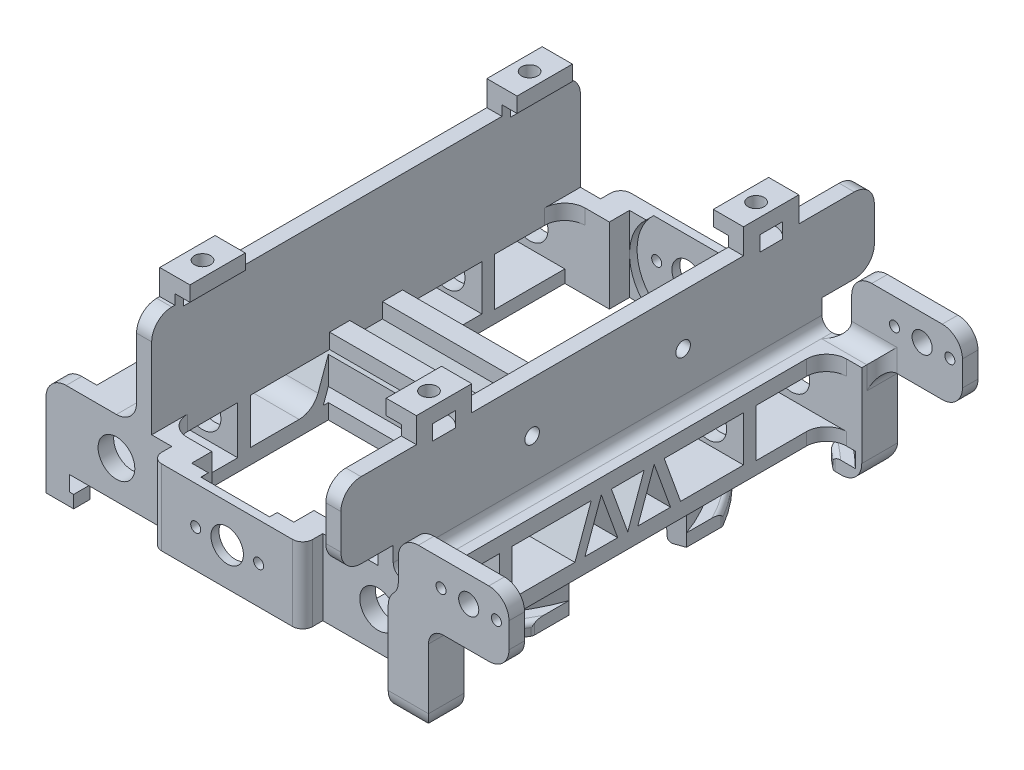
SolidWorks part; units mm, degrees
note: The reader was unsure of these and kept them because the rebuilt part matched: shared geometry of "草图50<4>".
ref_plane "前视基准面" through (0, 0, 0) normal (0, 0, 1) x (1, 0, 0)
ref_plane "上视基准面" through (0, 0, 0) normal (0, 1, 0) x (1, 0, 0)
ref_plane "右视基准面" through (0, 0, 0) normal (1, 0, 0) x (0, 0, -1)
sketch "草图1" plane through (0, 0, 0) normal (0, 0, 1) x (1, 0, 0)
  line L0 (-40, 0) -> (40, 0) construction
  line L1 (-40, 7.5) -> (40, 7.5)
  line L2 (-40, 7.5) -> (-40, -7.5)
  line L3 (-40, -7.5) -> (40, -7.5)
  line L4 (40, 7.5) -> (40, -7.5)
  line L5 (-40, 7.5) -> (40, -7.5) construction
  line L6 (-40, -7.5) -> (40, 7.5) construction
  line L7 (34, 6) -> (56, 6)
  line L8 (34, 6) -> (34, 19)
  line L9 (34, 19) -> (56, 19)
  line L10 (56, 6) -> (56, 19)
  point P0 (0, 0)
  dimension "D1" = 80
  dimension "D2" = 15
  dimension "D3" = 13
  dimension "D4" = 22
  dimension "D5" = 6
  dimension "D6" = 34
extrude "凸台-拉伸1" add sketch "草图1" along normal blind 7.1 contours L7 L10 L9 L8 L1 L4 | L7 L8 L1 L2 L3 L4 | L8 L7 L4 L1
sketch "草图2" plane through (0, 0, 7.1) normal (0, 0, 1) x (1, 0, 0)
  line L0 (-40, 0) -> (40, 0) construction
  line L1 (-40, 7.5) -> (-40, -7.5) construction
  line L2 (40, 6) -> (40, -7.5) construction
  circle A0 centre (0, 0) radius 3.225
  circle A1 centre (-26, 0) radius 3.65
  circle A2 centre (26, 0) radius 3.65
  circle A3 centre (6.25, 0) radius 1
  circle A4 centre (-6.25, 0) radius 1
  circle A5 centre (48, 13.8564) radius 2
  circle A6 centre (53.5, 13.8564) radius 1
  circle A7 centre (42.5, 13.8564) radius 1
  dimension "D1" = 2
  dimension "D2" = 2
  dimension "D3" = 2
  dimension "D4" = 2
  dimension "D5" = 6.45
  dimension "D6" = 6.25
  dimension "D10" = 7.3
  dimension "D11" = 7.3
  dimension "D16" = 4
  dimension "D7" = 6.25
  dimension "D8" = 26
  dimension "D9" = 26
  dimension "D12" = 26
  dimension "D13" = 5.5
  dimension "D14" = 5.5
  dimension "D15" = 22
extrude "切除-拉伸1" cut sketch "草图2" against normal through all contours A2 | A5 | A6 | A7 | A0 | A3 | A4 | A1
sketch "草图7" plane through (0, 0, 7.1) normal (0, 0, 1) x (1, 0, 0)
  line L0 (-40, -7.5) -> (40, -7.5) construction
  line L5 (-10.15, 7.5) -> (10.15, 7.5)
  line L6 (-10.15, 7.5) -> (-10.15, -7.5)
  line L7 (-10.15, -7.5) -> (10.15, -7.5)
  line L8 (10.15, 7.5) -> (10.15, -7.5)
  line L9 (-10.15, 7.5) -> (10.15, -7.5) construction
  line L10 (-10.15, -7.5) -> (10.15, 7.5) construction
  line L11 (34, 19) -> (34, 7.5)
  line L12 (34, 7.5) -> (40, 7.5)
  line L13 (40, 7.5) -> (40, 6)
  line L14 (40, 6) -> (56, 6)
  line L15 (56, 6) -> (56, 19)
  line L19 (34, 19) -> (56, 19)
  point P6 (0, 0)
  dimension "D1" = 13
  dimension "D2" = 22
  dimension "D3" = 20.3
extrude "切除-拉伸3" cut sketch "草图7" against normal blind 4
sketch "草图11" plane through (0, 0, 0) normal (0, 0, -1) x (-1, 0, 0)
  line L0 (40, 7.5) -> (-34, 7.5) construction
  line L1 (40, -7.5) -> (15, -7.5)
  line L2 (40, -7.5) -> (40, 7.5)
  line L3 (40, 7.5) -> (15, 7.5)
  line L4 (15, -7.5) -> (15, 7.5)
  line L5 (40, -7.5) -> (-40, -7.5) construction
  line L6 (-15, 7.5) -> (-32, 7.5)
  line L7 (-15, 7.5) -> (-15, -7.5)
  line L8 (-15, -7.5) -> (-32, -7.5)
  line L9 (-32, 7.5) -> (-32, -7.5)
  dimension "D1" = 15
  dimension "D2" = 25
  dimension "D3" = 17
sketch "草图12" plane through (0, 0, 3.1) normal (0, 0, 1) x (1, 0, 0)
  circle A0 centre (0, 0) radius 10.15
  dimension "D1" = 20.3
extrude "切除-拉伸6" cut sketch "草图12" against normal blind 1.5
extrude "切除-拉伸5" cut sketch "草图11" against normal blind 4
sketch "草图3" plane through (0, 0, 7.1) normal (0, 0, 1) x (1, 0, 0)
  line L1 (-33, 7.5) -> (-19, 7.5)
  line L2 (-33, 7.5) -> (-33, 4.5)
  line L3 (-33, 4.5) -> (-19, 4.5)
  line L4 (-19, 7.5) -> (-19, 4.5)
  line L5 (-33, 7.5) -> (-19, 4.5) construction
  line L6 (-33, 4.5) -> (-19, 7.5) construction
  line L7 (-40, 7.5) -> (-40, -7.5) construction
  line L8 (40, 7.5) -> (40, -7.5) construction
  line L9 (33, 4.5) -> (19, 4.5)
  line L10 (33, 4.5) -> (33, 7.5)
  line L11 (33, 7.5) -> (19, 7.5)
  line L12 (19, 4.5) -> (19, 7.5)
  line L13 (33, 4.5) -> (19, 7.5) construction
  line L14 (33, 7.5) -> (19, 4.5) construction
  line L15 (-40, 7.5) -> (-10.15, 7.5) construction
  line L16 (10.15, 7.5) -> (40, 7.5) construction
  line L17 (-26, 4.5) -> (-26, 7.5) construction
  line L18 (26, 4.5) -> (26, 7.5) construction
  point P0 (-26, 6)
  point P9 (26, 6)
  dimension "D1" = 14
  dimension "D2" = 14
  dimension "D3" = 3
  dimension "D4" = 3
  dimension "D5" = 14
  dimension "D6" = 14
extrude "凸台-拉伸4" add sketch "草图3" along normal blind 39.5
sketch "草图13" plane through (0, 4.5, 0) normal (0, -1, 0) x (1, 0, 0)
  line L0 (19, 46.6) -> (19, 7.1) construction
  line L1 (19, 21.1) -> (33, 21.1)
  line L2 (19, 21.1) -> (19, 23.6)
  line L3 (19, 23.6) -> (33, 23.6)
  line L4 (33, 21.1) -> (33, 23.6)
  line L5 (33, 46.6) -> (33, 7.1) construction
  line L6 (-33, 46.6) -> (-33, 7.1) construction
  line L7 (-33, 21.1) -> (-19, 21.1)
  line L8 (-33, 21.1) -> (-33, 23.6)
  line L9 (-33, 23.6) -> (-19, 23.6)
  line L10 (-19, 21.1) -> (-19, 23.6)
  line L11 (-19, 46.6) -> (-19, 7.1) construction
  line L12 (-40, 7.1) -> (-10.15, 7.1) construction
  line L13 (10.15, 7.1) -> (40, 7.1) construction
  line L14 (-33, 46.6) -> (-19, 46.6) construction
  dimension "D1" = 14
  dimension "D2" = 2.5
  dimension "D3" = 14
  dimension "D4" = 2.5
  dimension "D5" = 23
extrude "凸台-拉伸5" add sketch "草图13" along normal blind 12
sketch "草图15" plane through (0, 0, 23.6) normal (0, 0, 1) x (1, 0, 0)
  circle A0 centre (26, 0) radius 3.65
  circle A1 centre (-26, 0) radius 3.65
  dimension "D1" = 7.3
  dimension "D2" = 7.3
extrude "切除-拉伸7" cut sketch "草图15" against normal up to next
sketch "草图16" plane through (0, 0, 7.1) normal (0, 0, 1) x (1, 0, 0)
  line L0 (-19, -7.5) -> (-19, 4.5) construction
  line L1 (-33, -7.5) -> (-19, -7.5)
  line L2 (-33, -7.5) -> (-33, -5)
  line L3 (-33, -5) -> (-19, -5)
  line L4 (-19, -7.5) -> (-19, -5)
  line L9 (33, -7.5) -> (33, 4.5) construction
  line L10 (19, -7.5) -> (33, -7.5)
  line L11 (19, -7.5) -> (19, -5)
  line L12 (19, -5) -> (33, -5)
  line L13 (33, -7.5) -> (33, -5)
  dimension "D1" = 2.5
  dimension "D2" = 2.5
extrude "凸台-拉伸6" add sketch "草图16" along normal up to next
sketch "草图19" plane through (0, 0, 23.6) normal (0, 0, 1) x (1, 0, 0)
  line L0 (-19, -7.5) -> (-19, 4.5) construction
  line L1 (-33, -7.5) -> (-19, -7.5)
  line L2 (-33, -7.5) -> (-33, -4.5)
  line L3 (-33, -4.5) -> (-19, -4.5)
  line L4 (-19, -7.5) -> (-19, -4.5)
  line L5 (33, -7.5) -> (33, 4.5) construction
  line L6 (19, -7.5) -> (33, -7.5)
  line L7 (19, -7.5) -> (19, -4.5)
  line L8 (19, -4.5) -> (33, -4.5)
  line L9 (33, -7.5) -> (33, -4.5)
  dimension "D1" = 3
  dimension "D2" = 3
extrude "凸台-拉伸7" add sketch "草图19" along normal blind 23
sketch "草图20" plane through (-33, 0, 0) normal (-1, 0, 0) x (0, 0, 1)
  line L0 (36.1, -4.5) -> (39.35, 4.5)
  line L1 (36.1, -4.5) -> (38.1, -4.5)
  line L2 (39.35, 4.5) -> (41.35, 4.5)
  line L3 (38.1, -4.5) -> (41.35, 4.5)
  line L4 (46.6, -4.5) -> (23.6, -4.5) construction
  line L5 (46.6, 4.5) -> (23.6, 4.5) construction
  line L6 (41.35, 4.5) -> (43.35, 4.5)
  line L7 (41.35, 4.5) -> (44.6, -4.5)
  line L8 (43.35, 4.5) -> (46.6, -4.5)
  line L9 (44.6, -4.5) -> (46.6, -4.5)
  line L10 (23.6, -4.5) -> (23.6, 4.5) construction
  line M13 (46.6, -4.5) -> (23.6, -4.5)
  line M15 (23.6, 4.5) -> (46.6, 4.5)
  dimension "D1" = 12.5
  dimension "D2" = 10.5
  dimension "D3" = 5.25
  dimension "D4" = 2
  dimension "D5" = 2
extrude "凸台-拉伸10" add sketch "草图20" against normal blind 14 contours L3 L0 M13 M15 | L8 L7 M15 M13
sketch "草图21" plane through (-19, 0, 0) normal (1, 0, 0) x (0, 0, -1)
  line L0 (-46.6, -4.5) -> (-44.6, -4.5)
  line L1 (-46.6, -4.5) -> (-43.35, 4.5)
  line L2 (-44.6, -4.5) -> (-41.35, 4.5)
  line L3 (-43.35, 4.5) -> (-41.35, 4.5)
  line L4 (-41.35, 4.5) -> (-38.1, -4.5)
  line L5 (-41.35, 4.5) -> (-39.35, 4.5)
  line L6 (-38.1, -4.5) -> (-36.1, -4.5)
  line L7 (-39.35, 4.5) -> (-36.1, -4.5)
  line L8 (-46.6, 7.5) -> (-7.1, 7.5) construction
  line L9 (-43.35, 4.5) -> (-39.35, 4.5)
  line L10 (-43.35, 4.5) -> (-43.35, 7.5)
  line L11 (-43.35, 7.5) -> (-39.35, 7.5)
  line L12 (-39.35, 4.5) -> (-39.35, 7.5)
  line L13 (-7.1, -7.5) -> (-46.6, -7.5) construction
  line L14 (-46.6, -4.5) -> (-36.1, -4.5)
  line L15 (-46.6, -4.5) -> (-46.6, -7.5)
  line L16 (-46.6, -7.5) -> (-36.1, -7.5)
  line L17 (-36.1, -4.5) -> (-36.1, -7.5)
  line M3 (-46.6, -4.5) -> (-46.6, -7.5)
  line M4 (-46.6, -7.5) -> (-7.1, -7.5)
  line M10 (-7.1, 7.5) -> (-46.6, 7.5)
  line M14 (-38.1, -4.5) -> (-44.6, -4.5)
extrude "凸台-拉伸11" add sketch "草图21" along normal up to surface (38 mm away) contours L5 L12 L10 L3 M10 | L17 L6 L0 M14 M3 M4 up to face at (19, -0.0833, 25.35)
sketch "草图24" plane through (-19, 0, 0) normal (1, 0, 0) x (0, 0, -1)
  line L0 (-46.6, -4.5) -> (-44.6, -4.5)
  line L1 (-46.6, -4.5) -> (-43.35, 4.5)
  line L2 (-44.6, -4.5) -> (-41.35, 4.5)
  line L3 (-43.35, 4.5) -> (-41.35, 4.5)
  line L4 (-41.35, 4.5) -> (-39.35, 4.5)
  line L5 (-41.35, 4.5) -> (-38.1, -4.5)
  line L6 (-39.35, 4.5) -> (-36.1, -4.5)
  line L7 (-38.1, -4.5) -> (-36.1, -4.5)
extrude "凸台-拉伸12" add sketch "草图24" along normal up to surface (52 mm away) contours L5 L7 L6 L4
fillet "圆角1" radius 3 4 edges at (40, 6, 1.55) (34, 7.5, 1.55) (40, 6.75, 3.1) (37, 7.5, 3.1)
sketch "草图25" plane through (0, 7.5, 0) normal (0, 1, 0) x (1, 0, 0)
  line L0 (26, -46.6) -> (29, -46.6)
  line L1 (26, -46.6) -> (26, 6.4)
  line L2 (29, -46.6) -> (29, 6.4)
  line L3 (26, 6.4) -> (29, 6.4)
  line L4 (33, -46.6) -> (19, -46.6) construction
  dimension "D1" = 3
  dimension "D2" = 53
extrude "凸台-拉伸13" add sketch "草图25" along normal blind 20
sketch "草图26" plane through (0, 7.5, 0) normal (0, -1, 0) x (1, 0, 0)
  line L1 (26, 4) -> (29, 4)
  line L2 (26, 4) -> (26, -6.4)
  line L3 (26, -6.4) -> (29, -6.4)
  line L4 (29, 4) -> (29, -6.4)
extrude "切除-拉伸8" cut sketch "草图26" against normal blind 5
sketch "草图28" plane through (-33, 0, 0) normal (-1, 0, 0) x (0, 0, 1)
  line L1 (7.1, -5) -> (46.6, -5)
  line L2 (7.1, -5) -> (7.1, -7.5)
  line L3 (7.1, -7.5) -> (46.6, -7.5)
  line L4 (46.6, -5) -> (46.6, -7.5)
extrude "凸台-拉伸14" add sketch "草图28" along normal blind 7
sketch "草图35" plane through (0, 7.5, 0) normal (0, 1, 0) x (1, 0, 0)
  line L0 (-19, -46.6) -> (-22, -46.6)
  line L1 (-19, -46.6) -> (-19, -4)
  line L2 (-22, -46.6) -> (-22, -4)
  line L3 (-19, -4) -> (-22, -4)
  line L4 (-19, -46.6) -> (-33, -46.6) construction
  line L6 (26, -4) -> (26, -46.6) construction
  line L7 (-40, -4) -> (-15, -4) construction
  dimension "D1" = 45
  dimension "D2" = 3
extrude "凸台-拉伸16" add sketch "草图35" along normal blind 20 contours L1 L3 L2 L0
sketch "草图40" plane through (0, 27.5, 0) normal (0, 1, 0) x (1, 0, 0)
  line L0 (29, -19.6) -> (29, -8.6)
  line L3 (29, -19.6) -> (26, -19.6)
  line L4 (29, -8.6) -> (26, -8.6)
  line L5 (26, -19.6) -> (26, -8.6)
  line L6 (29, -46.6) -> (29, -4) construction
  line L7 (26, -46.6) -> (29, -46.6) construction
  line L8 (-22, -19.6) -> (-22, -8.6)
  line L9 (-22, -19.6) -> (-19, -19.6)
  line L10 (-22, -8.6) -> (-19, -8.6)
  line L11 (-19, -19.6) -> (-19, -8.6)
  line L12 (-22, -46.6) -> (-22, -4) construction
  line L14 (-19, -46.6) -> (-19, -4) construction
  line L15 (-19, -46.6) -> (-22, -46.6) construction
  dimension "D1" = 3
  dimension "D2" = 11
  dimension "D3" = 27
  dimension "D4" = 27
  dimension "D5" = 11
extrude "凸台-拉伸18" add sketch "草图40" along normal blind 2
sketch "草图41" plane through (0, 29.5, 0) normal (0, 1, 0) x (1, 0, 0)
  line L0 (-19, -19.6) -> (-19, -8.6) construction
  line L5 (26, -19.6) -> (26, -8.6) construction
  circle A0 centre (26, -14.1) radius 3.75
  circle A1 centre (-19, -14.1) radius 3.75
  dimension "D1" = 7.5
  dimension "D2" = 7.5
extrude "切除-拉伸11" cut sketch "草图41" against normal blind 3 contours A0 | A1
sketch "草图43" plane through (0, 29.5, 0) normal (0, 1, 0) x (1, 0, 0)
  line L0 (29, -19.6) -> (29, -8.6)
  line L1 (29, -19.6) -> (23, -19.6)
  line L2 (29, -8.6) -> (23, -8.6)
  line L3 (23, -19.6) -> (23, -8.6)
  line L4 (29, -46.6) -> (29, -4) construction
  line L5 (26, -19.6) -> (29, -19.6) construction
  line L6 (-22, -8.6) -> (-22, -19.6)
  line L7 (-22, -8.6) -> (-16, -8.6)
  line L8 (-22, -19.6) -> (-16, -19.6)
  line L9 (-16, -8.6) -> (-16, -19.6)
  dimension "D1" = 6
  dimension "D2" = 6
extrude "凸台-拉伸19" add sketch "草图43" along normal blind 3
sketch "草图44" plane through (0, 32.5, 0) normal (0, 1, 0) x (1, 0, 0)
  line L0 (26, -8.6) -> (26, -19.6) construction
  line L1 (29, -8.6) -> (23, -8.6) construction
  line L2 (-19, -8.6) -> (-19, -19.6) construction
  line L3 (-16, -8.6) -> (-22, -8.6) construction
  line L4 (-22, -19.6) -> (-16, -19.6) construction
  circle A0 centre (26, -14.1) radius 1.6
  circle A1 centre (-19, -14.1) radius 1.6
  dimension "D1" = 3.2
  dimension "D2" = 3.2
extrude "切除-拉伸12" cut sketch "草图44" against normal blind 3
sketch "草图46" plane through (29, 0, 0) normal (1, 0, 0) x (0, 0, -1)
  line L0 (-46.6, 17.5) -> (6.4, 17.5) construction
  line L1 (-46.6, 27.5) -> (-46.6, 7.5) construction
  line L2 (6.4, 27.5) -> (6.4, 12.5) construction
  circle A0 centre (-31.6, 17.5) radius 1.45
  dimension "D1" = 2.9
  dimension "D2" = 15
sketch "草图48" plane through (0, -7.5, 0) normal (0, -1, 0) x (1, 0, 0)
  line L0 (-19, 36.1) -> (19, 36.1)
  line L1 (-19, 36.1) -> (-19, 39.1)
  line L2 (19, 36.1) -> (19, 39.1)
  line L3 (-19, 39.1) -> (19, 39.1)
  dimension "D1" = 3
extrude "切除-拉伸13" cut sketch "草图48" against normal through all
extrude "切除-拉伸14" cut sketch "草图46" against normal up to next
sketch "草图49" plane through (0, -5, 0) normal (0, 1, 0) x (1, 0, 0)
  line L0 (-36.5, -7.1) -> (-36.5, -46.6) construction
  line L1 (-40, -7.1) -> (-33, -7.1) construction
  line L2 (-40, -46.6) -> (-33, -46.6) construction
  line L3 (-40, -46.6) -> (-40, -7.1) construction
  circle A0 centre (-37.5, -26.6) radius 1.5
  circle A1 centre (-35, -31.6) radius 1.5
  dimension "D1" = 3
  dimension "D2" = 3
  dimension "D3" = 20
  dimension "D4" = 15
  dimension "D5" = 2.5
extrude "切除-拉伸15" cut sketch "草图49" against normal up to next
sketch "草图50" plane through (0, -7.5, 0) normal (0, -1, 0) x (1, 0, 0)
  line L0 (0, 0) -> (0, 46.6) construction
  line L1 (-40, 46.6) -> (33, 46.6) construction
  line L2 (19, 20.8512) -> (19, 13.691)
  line L3 (-40, 4) -> (-34.5, 4)
  line L4 (-40, 4) -> (-40, 9)
  line L5 (-40, 9) -> (-34.5, 9)
  line L6 (-34.5, 4) -> (-34.5, 9)
  line L11 (40, 0) -> (32, 0)
  line L12 (40, 0) -> (40, 7.1)
  line L13 (40, 7.1) -> (32, 7.1)
  line L14 (32, 0) -> (32, 7.1)
  line L15 (19, 39.1) -> (19, 7.1) construction
  line L16 (0, 46.6) -> (33, 34.9381)
  line L17 (33, 7.1) -> (33, 46.6) construction
  line L18 (33, 34.9381) -> (33, 27.7586)
  line L20 (-38, 46.6) -> (-31.5, 46.6)
  line L21 (-38, 46.6) -> (-38, 45.1)
  line L22 (-38, 45.1) -> (-31.5, 45.1)
  line L23 (-31.5, 46.6) -> (-31.5, 45.1)
  circle A0 centre (0, 46.6) radius 55.3215
  circle A1 centre (0, 46.6) radius 35
  circle A2 centre (0, 46.6) radius 32
  circle A3 centre (0, 46.6) radius 38
  circle A4 centre (0, 46.6) radius 52.3215
  line M17 (19, 39.1) -> (19, 7.1)
  line M27 (-40, 4) -> (-15, 4)
  line M32 (32, 4) -> (32, 0)
  line M33 (32, 0) -> (40, 0)
  line M34 (40, 0) -> (40, 7.1)
  line M35 (40, 7.1) -> (33, 7.1)
  line M36 (33, 7.1) -> (33, 46.6)
  line M38 (-40, 46.6) -> (-40, 4)
  dimension "D1" = 110.6431
  dimension "D6" = 70
  dimension "D7" = 3
  dimension "D8" = 3
  dimension "D9" = 3
  dimension "D2" = 5.5
  dimension "D3" = 5
  dimension "D4" = 8
  dimension "D5" = 7.1
  dimension "D10" = 6.5
  dimension "D11" = 1.5
extrude "凸台-拉伸20" add sketch "草图50" along normal blind 5.5 contours A0 L14 M33 M34 M35 | A4 L14 A0 L13 M32 | A4 L5 A0 L3 L6 M38 | A0 L4 M27 | L2 A3 A1 M36 | A2 A1 L16 M17 | A2 L20 A1 L22 | L20 A3 L22 A1
extrude "切除-拉伸16" cut sketch "草图50<4>" along normal blind 3 contours L2 A3 A1 M36 | A4 L5 A0 L3 L6 M38 | A4 L14 A0 L13 M32 | A2 L20 A1 L22
sketch "草图50<4>" plane through (0, -7.5, 0) normal (0, -1, 0) x (1, 0, 0) same geometry as "草图50"
fillet "圆角2" radius 4 6 edges at (36, -13, 0) (32, 7.6716, 2) (40, -13, 3.55) (34, 19, 1.55) (56, 19, 1.55) (56, 6, 1.55)
fillet "圆角3" radius 4 11 edges at (-40, 7.5, 5.55) (-19, 6, 7.1) (19, 6, 7.1) (33, 6, 7.1) (33, -6.25, 7.1) (-26, -4.5, 36.1) (27.5, 27.5, -6.4) (27.5, 12.5, -6.4) (-20.5, 27.5, 4) (-22, 7.5, 25.3) (25.7169, -7.5, 27.5568)
fillet "圆角4" radius 2 8 edges at (-15, 0, 0) (15, 0, 0) (-39, -7.5, 46.6) (30, 7.5, 4) (29, 7.5, 25.3) (-37.9926, -7.5, 45.8499) (-36.4691, -7.5, 45.1) (-37.9926, -13, 45.8499)
fillet "圆角5" radius 1 9 edges at (32, -11.75, 5.205) (34.3117, -11.75, 7.1) (33.1694, -10.5, 6.136) (26.9346, -10.5, 19.7947) (25.7169, -13, 27.5568) (19, -11.75, 13.691) (33, -11.75, 27.7586) (-31.9912, -10.5, 45.8498) (-31.9912, -13, 45.8498)
mirror "镜向2" about plane through (0, 0, 46.6) normal (0, 0, 1) of bodies 136
